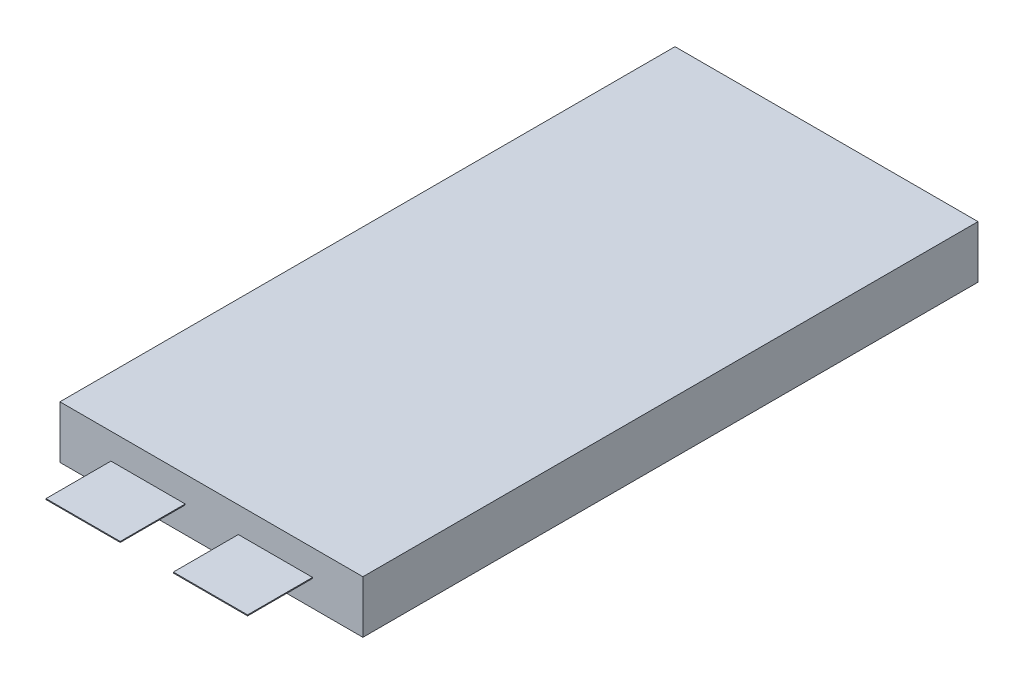
SolidWorks part; units mm, degrees
ref_plane "Front" through (0, 0, 0) normal (0, 0, 1) x (1, 0, 0)
ref_plane "Top" through (0, 0, 0) normal (0, 1, 0) x (1, 0, 0)
ref_plane "Right" through (0, 0, 0) normal (1, 0, 0) x (0, 0, -1)
sketch "Sketch1" plane through (0, 0, 0) normal (0, 0, 1) x (1, 0, 0)
  line L1 (-20.6742, 1.7083) -> (11.9858, 1.7083)
  line L2 (-20.6742, 1.7083) -> (-20.6742, -3.9517)
  line L3 (-20.6742, -3.9517) -> (11.9858, -3.9517)
  line L4 (11.9858, 1.7083) -> (11.9858, -3.9517)
  dimension "D1" = 32.66
  dimension "D2" = 5.66
extrude "Boss-Extrude1" add sketch "Sketch1" along normal blind 66.3
sketch3d "3DSketch1"
  line L0 (-20.6742, 1.7083, 66.3) -> (-20.6742, -3.9517, 66.3) construction
  line L1 (-20.6742, -1.1217, 66.3) -> (-15.1742, -1.1217, 66.3) construction
  line L2 (-4.3442, -1.1217, 66.3) -> (-1.4442, -1.1217, 66.3) construction
  line L4 (-4.3442, 1.7083, 66.3) -> (-4.3442, -3.9517, 66.3) construction
  line L6 (-15.1742, -1.1217, 66.3) -> (-4.3442, -1.1217, 66.3) construction
  line L7 (-15.1742, -1.1217, 66.3) -> (-7.1742, -1.1217, 66.3) construction
  line L8 (6.5558, -1.0684, 66.3) -> (-1.4442, -1.0684, 66.3) construction
  line L10 (-15.1742, -1.1784, 66.3) -> (-7.1742, -1.1784, 66.3)
  line L11 (-15.1742, -1.1784, 66.3) -> (-15.1742, -1.0784, 66.3)
  line L12 (-15.1742, -1.0784, 66.3) -> (-7.1742, -1.0784, 66.3)
  line L13 (-7.1742, -1.1784, 66.3) -> (-7.1742, -1.0784, 66.3)
  line L14 (-15.1742, -1.1784, 66.3) -> (-7.1742, -1.0784, 66.3) construction
  line L15 (-15.1742, -1.0784, 66.3) -> (-7.1742, -1.1784, 66.3) construction
  line L16 (-1.4442, -1.1726, 66.3) -> (6.5558, -1.1707, 66.3)
  line L17 (-1.4442, -1.1726, 66.3) -> (-1.4442, -1.0707, 66.3)
  line L18 (-1.4442, -1.0707, 66.3) -> (6.5558, -1.0687, 66.3)
  line L19 (6.5558, -1.1707, 66.3) -> (6.5558, -1.0687, 66.3)
  line L20 (-1.4442, -1.1726, 66.3) -> (6.5558, -1.0687, 66.3) construction
  line L21 (-1.4442, -1.0707, 66.3) -> (6.5558, -1.1707, 66.3) construction
  point P6 (-11.1742, -1.1217, 66.3)
  point P15 (-11.1742, -1.1784, 66.3)
  point P16 (-1.4442, -1.1217, 66.3)
  point P18 (2.5558, -1.0684, 66.3)
  point P25 (2.5558, -1.0684, 66.3)
  dimension "D1" = 8
  dimension "D2" = 0.1
  dimension "D4" = 0.1
  dimension "D3" = 8
extrude "Boss-Extrude3" add sketch "3DSketch1" along direction (0, 0, -1) on the side against the normal blind 7
sketch3d "3DSketch2"
  line L1 (-14.0004, -3.9517, 62.7689) -> (-8.8677, -3.9517, 62.7689)
  line L2 (-14.0004, -3.9517, 62.7689) -> (-14.0004, -3.9517, 63.1495)
  line L3 (-14.0004, -3.9517, 63.1495) -> (-8.8677, -3.9517, 63.1495)
  line L4 (-8.8677, -3.9517, 62.7689) -> (-8.8677, -3.9517, 63.1495)
  line L5 (-14.0004, -3.9517, 62.7689) -> (-8.8677, -3.9517, 63.1495) construction
  line L6 (-14.0004, -3.9517, 63.1495) -> (-8.8677, -3.9517, 62.7689) construction
  circle A0 centre (-11.434, -3.9517, 62.9592) radius 2.9324
  circle A1 centre (-11.434, -3.9517, 62.9592) radius 3.0862
  point P2 (-11.434, -6.8841, 62.9592)
  point P8 (-11.434, -7.0378, 62.9592)
extrude "Cut-Extrude1" cut sketch "3DSketch2" along direction (0, -1, 0) on the side of the normal blind 0.1
